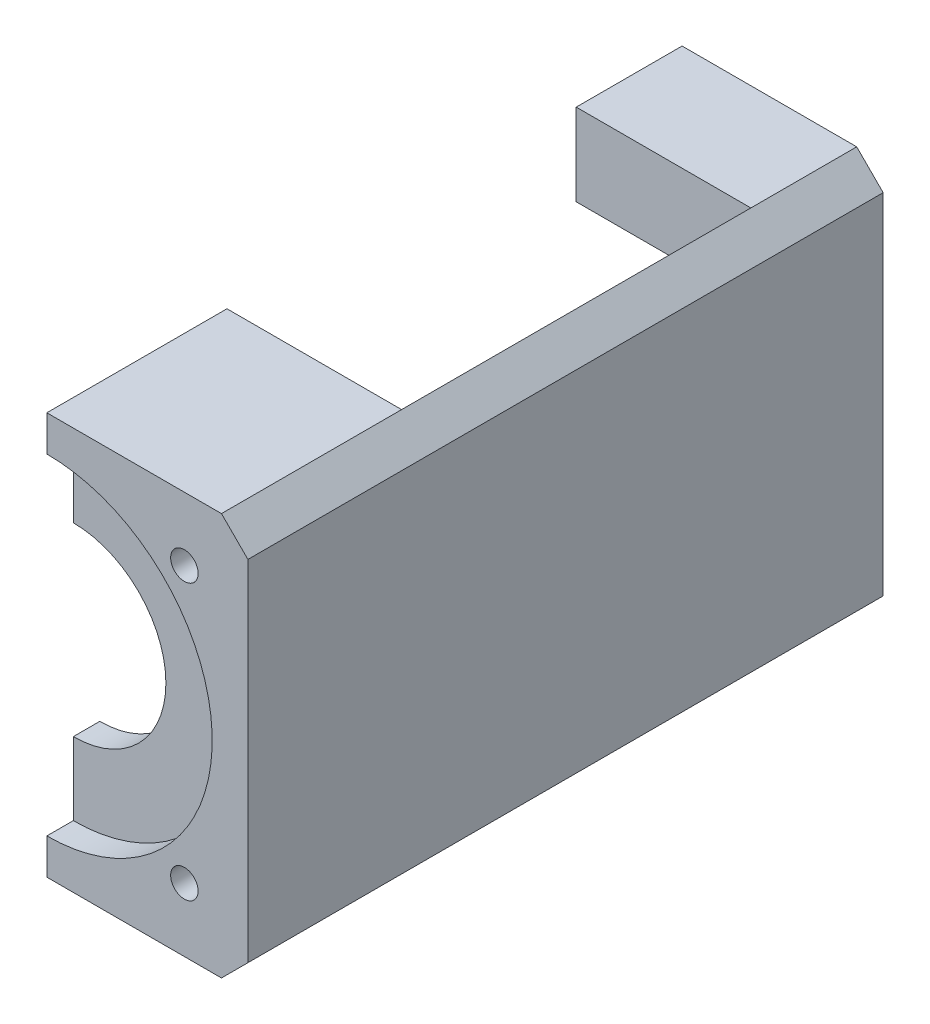
SolidWorks part; units mm, degrees
material "2024-T3"
ref_plane "Front Plane" through (0, 0, 0) normal (0, 0, 1) x (1, 0, 0)
ref_plane "Top Plane" through (0, 0, 0) normal (0, 1, 0) x (1, 0, 0)
ref_plane "Right Plane" through (0, 0, 0) normal (1, 0, 0) x (0, 0, -1)
sketch "Sketch1" plane through (0, 0, 0) normal (0, 0, 1) x (1, 0, 0)
  line L0 (0, 0) -> (41.91, 41.91) construction
  line L1 (0, 0) -> (41.91, 0)
  line L2 (0, 0) -> (0, 41.91)
  line L3 (0, 41.91) -> (41.91, 41.91)
  line L4 (41.91, 0) -> (41.91, 41.91)
  line L5 (4.4493, 37.4607) -> (20.955, 20.955) construction
  circle A0 centre (37.4607, 37.4607) radius 1.6497
  circle A1 centre (37.4607, 4.4493) radius 1.6497
  circle A2 centre (4.4493, 4.4493) radius 1.6497
  circle A3 centre (4.4493, 37.4607) radius 1.6497
  circle A4 centre (20.955, 20.955) radius 11.1125
  point P7 (20.955, 20.955)
  point P17 (20.955, 20.955)
  dimension "D3" = 3.2995
  dimension "D7" = 22.225
  dimension "D1" = 41.91
  dimension "D2" = 41.91
  dimension "D4" = 23.3426
  dimension "D6" = 23.3426
  dimension "D5" = 4
extrude "Boss-Extrude1" add sketch "Sketch1" along normal blind 6.35
sketch "Sketch2" plane through (0, 0, 6.35) normal (0, 0, 1) x (1, 0, 0)
  circle A0 centre (20.955, 20.955) radius 27.7876
  circle A1 centre (20.955, 20.955) radius 62.5657
  dimension "D1" = 55.5752
extrude "Cut-Extrude1" cut sketch "Sketch2" against normal through all
sketch "Sketch3" plane through (0, 0, 6.35) normal (0, 0, 1) x (1, 0, 0)
  circle A0 centre (20.955, 20.955) radius 19.8438
  dimension "D1" = 39.6875
extrude "Cut-Extrude2" cut sketch "Sketch3" against normal blind 3.175
sketch "Sketch4" plane through (0, 0, 6.35) normal (0, 0, 1) x (1, 0, 0)
  line L0 (0, 39.2043) -> (0, 2.7057) construction
  line L1 (-3.175, 45.085) -> (45.085, 45.085)
  line L2 (-3.175, 45.085) -> (-3.175, -3.175)
  line L3 (-3.175, -3.175) -> (45.085, -3.175)
  line L4 (45.085, 45.085) -> (45.085, -3.175)
  line L5 (39.2043, 41.91) -> (2.7057, 41.91) construction
  line L6 (41.91, 2.7057) -> (41.91, 39.2043) construction
  line L7 (2.7057, 0) -> (39.2043, 0) construction
  line L12 (0, 39.2043) -> (0, 2.7057)
  line L13 (2.7057, 0) -> (39.2043, 0)
  line L14 (41.91, 2.7057) -> (41.91, 39.2043)
  line L15 (39.2043, 41.91) -> (2.7057, 41.91)
  line L16 (0, 39.2043) -> (0, 2.7057)
  line L17 (2.7057, 0) -> (39.2043, 0)
  line L18 (41.91, 2.7057) -> (41.91, 39.2043)
  line L19 (39.2043, 41.91) -> (2.7057, 41.91)
  arc A4 (2.7057, 41.91) -> (0, 39.2043) centre (20.955, 20.955) ccw
  arc A5 (0, 2.7057) -> (2.7057, 0) centre (20.955, 20.955) ccw
  arc A6 (39.2043, 0) -> (41.91, 2.7057) centre (20.955, 20.955) ccw
  arc A7 (41.91, 39.2043) -> (39.2043, 41.91) centre (20.955, 20.955) ccw
  arc A8 (2.7057, 41.91) -> (0, 39.2043) centre (20.955, 20.955) ccw
  arc A9 (0, 2.7057) -> (2.7057, 0) centre (20.955, 20.955) ccw
  arc A10 (39.2043, 0) -> (41.91, 2.7057) centre (20.955, 20.955) ccw
  arc A11 (41.91, 39.2043) -> (39.2043, 41.91) centre (20.955, 20.955) ccw
  dimension "D1" = 3.175
  dimension "D2" = 3.175
  dimension "D3" = 3.175
  dimension "D4" = 3.175
  dimension "D5" = 0
extrude "Boss-Extrude2" add sketch "Sketch4" against normal up to surface (6.35 mm away) up to face at (6.099, 4.4493, 0)
ref_plane "Plane1" through (20.955, 0, 0) normal (1, 0, 0) x (0, 0, -1)
sketch "Sketch5" plane through (-3.175, 0, 0) normal (-1, 0, 0) x (0, 0, 1)
  line L4 (6.35, 45.085) -> (0, 45.085)
  line L5 (0, 45.085) -> (0, -3.175)
  line L6 (0, -3.175) -> (6.35, -3.175)
  line L7 (6.35, -3.175) -> (6.35, 45.085)
  line L8 (6.35, 45.085) -> (0, 45.085)
  line L9 (0, 45.085) -> (0, -3.175)
  line L10 (0, -3.175) -> (6.35, -3.175)
  line L11 (6.35, -3.175) -> (6.35, 45.085)
  dimension "D1" = 0
extrude "Cut-Extrude3" cut sketch "Sketch5" against normal up to surface (24.13 mm away) up to plane "Plane1"
sketch "Sketch6" plane through (0, 0, 0) normal (0, 0, -1) x (-1, 0, 0)
  line L0 (-45.085, -3.175) -> (-45.085, 45.085) construction
  line L1 (-20.955, -3.175) -> (-45.085, -3.175)
  line L2 (-20.955, -3.175) -> (-20.955, 0)
  line L3 (-20.955, 0) -> (-45.085, 0)
  line L4 (-45.085, -3.175) -> (-45.085, 0)
  line L5 (-45.085, 45.085) -> (-20.955, 45.085) construction
  line L6 (-45.085, -3.175) -> (-41.91, -3.175)
  line L7 (-45.085, -3.175) -> (-45.085, 45.085)
  line L8 (-45.085, 45.085) -> (-41.91, 45.085)
  line L9 (-41.91, -3.175) -> (-41.91, 45.085)
  line L10 (-20.955, 45.085) -> (-20.955, 32.0675) construction
  line L11 (-45.085, 45.085) -> (-20.955, 45.085)
  line L12 (-45.085, 45.085) -> (-45.085, 41.91)
  line L13 (-45.085, 41.91) -> (-20.955, 41.91)
  line L14 (-20.955, 45.085) -> (-20.955, 41.91)
  line M1 (-20.955, 32.0675) -> (-20.955, 45.085)
  line M2 (-20.955, 45.085) -> (-45.085, 45.085)
  line M3 (-45.085, 45.085) -> (-45.085, -3.175)
  line M4 (-45.085, -3.175) -> (-20.955, -3.175)
  line M5 (-20.955, -3.175) -> (-20.955, 9.8425)
  dimension "D1" = 3.175
  dimension "D2" = 3.175
  dimension "D3" = 3.175
extrude "Boss-Extrude3" add sketch "Sketch6" along normal blind 57.1754 contours L9 L1 L3 M5 | L9 L3 M4 M3 | L13 L7 L3 L9 | L13 L9 M3 M2 | L9 L13 M1 M2 region at (31.4325, -1.5875, 0) region at (43.4975, -1.5875, 0) region at (43.4975, 20.955, 0) region at (43.4975, 43.4975, 0) region at (31.4325, 43.4975, 0)
sketch "Sketch8" plane through (0, 0, -57.1754) normal (0, 0, -1) x (-1, 0, 0)
  line L1 (-45.085, 45.085) -> (-20.955, 45.085)
  line L2 (-45.085, 45.085) -> (-45.085, -3.175)
  line L3 (-45.085, -3.175) -> (-20.955, -3.175)
  line L4 (-20.955, 45.085) -> (-20.955, -3.175)
extrude "Boss-Extrude4" add sketch "Sketch8" along normal blind 6.35
sketch "Sketch10" plane through (0, 0, 0) normal (0, 1, 0) x (1, 0, 0)
  line L0 (20.955, 15.2654) -> (41.91, 15.2654)
  line L4 (20.955, 0) -> (41.91, 0)
  line L5 (41.91, 0) -> (41.91, 57.1754)
  line L6 (41.91, 57.1754) -> (20.955, 57.1754)
  line L7 (20.955, 57.1754) -> (20.955, 0)
  line L8 (20.955, 0) -> (41.91, 0)
  line L9 (41.91, 0) -> (41.91, 57.1754)
  line L10 (41.91, 57.1754) -> (20.955, 57.1754)
  line L11 (20.955, 57.1754) -> (20.955, 0)
  line M6 (41.91, 0) -> (41.91, 57.1754)
  line M7 (41.91, 57.1754) -> (20.955, 57.1754)
  line M8 (20.955, 57.1754) -> (20.955, 0)
  dimension "D2" = 41.91
  dimension "D1" = 0
extrude "Cut-Extrude6" cut sketch "Sketch10" along normal through all contours L0 M8 M6 M7 region at (31.4325, 0, -36.2204)
chamfer "Chamfer1" distance 3.175 angle 45 2 edges at (45.085, -3.175, -28.5877) (45.085, 45.085, -28.5877)
sketch "Sketch11" plane through (20.955, 0, 0) normal (-1, 0, 0) x (0, 0, 1)
  circle A0 centre (0, 41.91) radius 1.5875
  circle A1 centre (0, 0) radius 1.5875
  dimension "D1" = 3.175
extrude "Cut-Extrude7" cut sketch "Sketch11" against normal up to surface (20.955 mm away) up to face at (41.91, 28.9983, -24.1469)
fillet "Fillet1" radius 6.6675 1 edges
sketch "Sketch13" plane through (0, 0, -63.5254) normal (0, 0, -1) x (-1, 0, 0)
  line L6 (-45.085, 41.91) -> (-45.085, 0)
  line L7 (-45.085, 0) -> (-41.91, -3.175)
  line L8 (-41.91, -3.175) -> (-20.955, -3.175)
  line L9 (-20.955, -3.175) -> (-20.955, 45.085)
  line L10 (-20.955, 45.085) -> (-41.91, 45.085)
  line L11 (-41.91, 45.085) -> (-45.085, 41.91)
  line L12 (-45.085, 41.91) -> (-45.085, 0)
  line L13 (-45.085, 0) -> (-41.91, -3.175)
  line L14 (-41.91, -3.175) -> (-20.955, -3.175)
  line L15 (-20.955, -3.175) -> (-20.955, 45.085)
  line L16 (-20.955, 45.085) -> (-41.91, 45.085)
  line L17 (-41.91, 45.085) -> (-45.085, 41.91)
  dimension "D1" = 0
extrude "Boss-Extrude6" add sketch "Sketch13" along normal blind 6.35
sketch "Sketch14" plane through (0, 0, -69.8754) normal (0, 0, -1) x (-1, 0, 0)
  line L0 (-20.955, -3.175) -> (-20.955, 45.085) construction
  line L1 (-6.6675, 6.6675) -> (-35.2425, 6.6675)
  line L2 (-6.6675, 6.6675) -> (-6.6675, 35.2425)
  line L3 (-6.6675, 35.2425) -> (-35.2425, 35.2425)
  line L4 (-35.2425, 6.6675) -> (-35.2425, 35.2425)
  line L5 (-6.6675, 6.6675) -> (-35.2425, 35.2425) construction
  line L6 (-6.6675, 35.2425) -> (-35.2425, 6.6675) construction
  point P0 (-20.955, 20.955)
  dimension "D1" = 28.575
extrude "Cut-Extrude8" cut sketch "Sketch14" against normal blind 12.7
chamfer "Chamfer2" distance 1.5875 angle 45 3 edges at (28.0988, 35.2425, -69.8754) (35.2425, 20.955, -69.8754) (28.0988, 6.6675, -69.8754)
